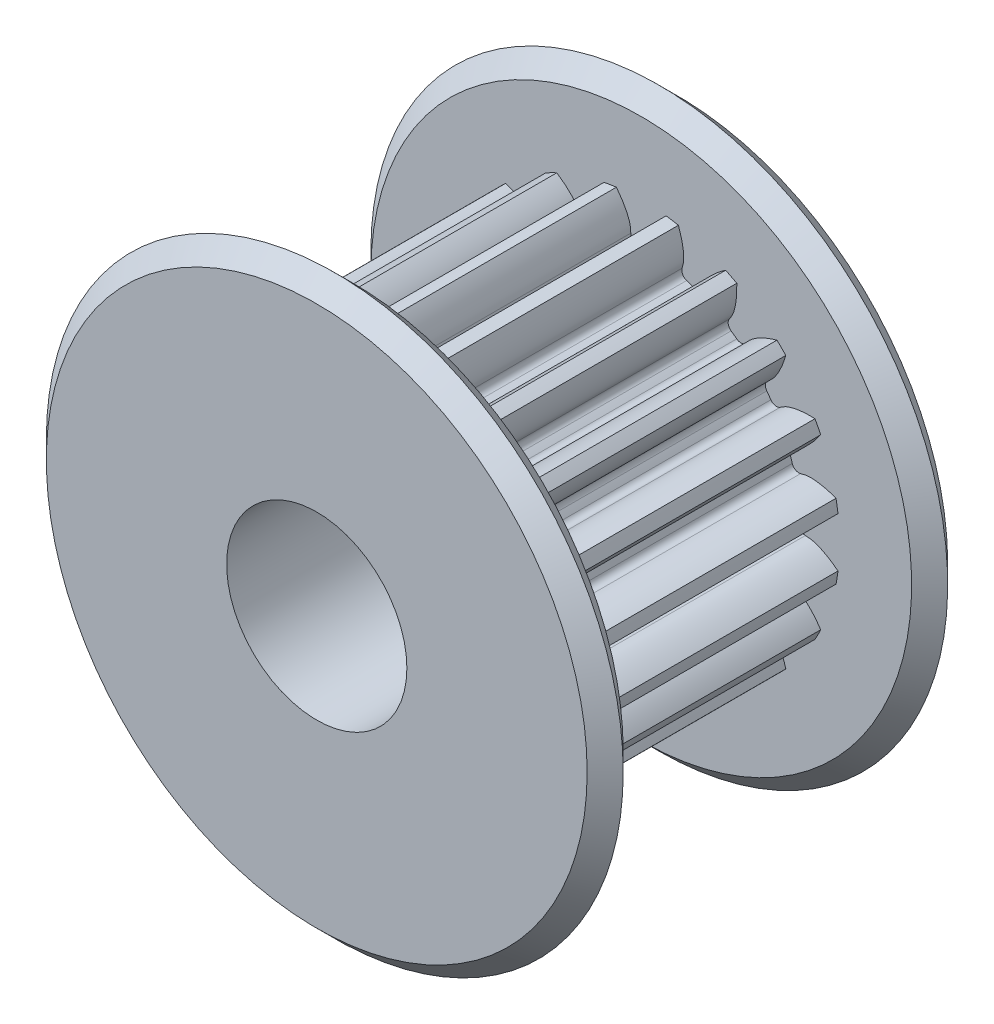
SolidWorks part; units mm, degrees
ref_plane "前视基准面" through (0, 0, 0) normal (0, 0, 1) x (1, 0, 0)
ref_plane "上视基准面" through (0, 0, 0) normal (0, 1, 0) x (1, 0, 0)
ref_plane "右视基准面" through (0, 0, 0) normal (1, 0, 0) x (0, 0, -1)
ref_axis "Axis1" through (0, 0, -88.99) along (0, 0, 1)
sketch "草图1" plane through (0, 0, 0) normal (0, 0, 1) x (1, 0, 0)
  circle A0 centre (0, 0) radius 5.5
extrude "LaShenA" add sketch "草图1" along normal blind 8
sketch "SketchA" plane through (0, 0, 8) normal (0, 0, 1) x (1, 0, 0)
  line L0 (0, 0) -> (0, 5.5) construction
  arc A0 (0.0963, 4.3739) -> (-0.0963, 4.3739) centre (0, 0) ccw
  arc A1 (0.8966, 5.6915) -> (-0.8966, 5.6915) centre (0, 0) ccw
  arc A2 (-0.0963, 4.3739) -> (-0.2902, 4.5522) centre (-0.1005, 4.5639) cw
  arc A3 (0.2902, 4.5522) -> (0.0963, 4.3739) centre (0.1005, 4.5639) cw
  circle A4 centre (0, 0) radius 4.6985 construction
  circle A5 centre (0, 0) radius 5.5 construction
  circle A6 centre (0, 0) radius 4.375 construction
  circle A7 centre (0, 0) radius 5 construction
  spline S0 degree 3 poles (0.2902, 4.5522) (0.293, 4.5981) (0.2941, 4.6581) (0.304, 4.7242) (0.3102, 4.7521) (0.3156, 4.7742) (0.3226, 4.7995) (0.3313, 4.828) (0.3419, 4.8596) (0.3546, 4.8941) (0.3694, 4.9315) (0.3867, 4.9717) (0.4065, 5.0147) (0.4291, 5.0602) (0.4545, 5.1081) (0.4829, 5.1584) (0.5145, 5.2109) (0.5494, 5.2655) (0.5878, 5.322) (0.6297, 5.3803) (0.6754, 5.4402) (0.7248, 5.5015) (0.7975, 5.5868) (0.8558, 5.6498) (0.8966, 5.6915) knots 0.125068 0.125068 0.125068 0.125068 0.215847 0.244833 0.257593 0.272674 0.290074 0.309794 0.331834 0.356194 0.382875 0.411875 0.443195 0.476835 0.512796 0.551076 0.591676 0.634597 0.679837 0.727398 0.777278 0.829478 0.883999 1 1 1 1
  spline S1 degree 3 poles (-0.2902, 4.5522) (-0.293, 4.5981) (-0.2941, 4.6581) (-0.304, 4.7242) (-0.3102, 4.7521) (-0.3156, 4.7742) (-0.3226, 4.7995) (-0.3313, 4.828) (-0.3419, 4.8596) (-0.3546, 4.8941) (-0.3694, 4.9315) (-0.3867, 4.9717) (-0.4065, 5.0147) (-0.4291, 5.0602) (-0.4545, 5.1081) (-0.4829, 5.1584) (-0.5145, 5.2109) (-0.5494, 5.2655) (-0.5878, 5.322) (-0.6297, 5.3803) (-0.6754, 5.4402) (-0.7248, 5.5015) (-0.7975, 5.5868) (-0.8558, 5.6498) (-0.8966, 5.6915) knots 0.125068 0.125068 0.125068 0.125068 0.215847 0.244833 0.257593 0.272674 0.290074 0.309794 0.331834 0.356194 0.382875 0.411875 0.443195 0.476835 0.512796 0.551076 0.591676 0.634597 0.679837 0.727398 0.777278 0.829478 0.883999 1 1 1 1
  dimension "D1" = 0.19
  dimension "Db" = 9.3969
  dimension "Da" = 11
  dimension "Df" = 8.75
  dimension "Dn" = 10
extrude "Cut-ExtrudeA" cut sketch "SketchA" against normal blind 8
pattern_circular "阵列(圆周)1" count 20 over 360 about axis through (0, 0, -88.99) along (0, 0, 1) of "Cut-ExtrudeA"
sketch "草图3" plane through (0, 0, 8) normal (0, 0, 1) x (1, 0, 0)
  circle A0 centre (0, 0) radius 8
  dimension "D1" = 16
extrude "凸台-拉伸2" add sketch "草图3" along normal blind 1
sketch "草图4" plane through (0, 0, 0) normal (0, 0, -1) x (-1, 0, 0)
  circle A0 centre (0, 0) radius 8
extrude "凸台-拉伸3" add sketch "草图4" along normal blind 6
chamfer "倒角1" distance 0.5 angle 45 4 edges at (-8, 0, -6) (-8, 0, 0) (8, 0, 8) (8, 0, 9)
sketch "草图5" plane through (0, 0, 9) normal (0, 0, 1) x (1, 0, 0)
  circle A0 centre (0, 0) radius 2.5
  dimension "D1" = 5
extrude "切除-拉伸2" cut sketch "草图5" against normal blind 16
sketch "草图6" plane through (0, 0, 0) normal (1, 0, 0) x (0, 0, -1)
  line L0 (5.5, 8) -> (0.5, 8) construction
  line L1 (1, 8) -> (6, 8)
  line L2 (1, 8) -> (1, -8)
  line L3 (1, -8) -> (6, -8)
  line L4 (6, 8) -> (6, -8)
  line L5 (0, 7.5) -> (0, -7.5) construction
  dimension "D1" = 5
  dimension "D2" = 16
  dimension "D3" = 1
extrude "切除-拉伸3" cut sketch "草图6" against normal blind 20 from offset 10
chamfer "倒角2" distance 0.5 angle 45 1 edges at (0, -8, -1)
